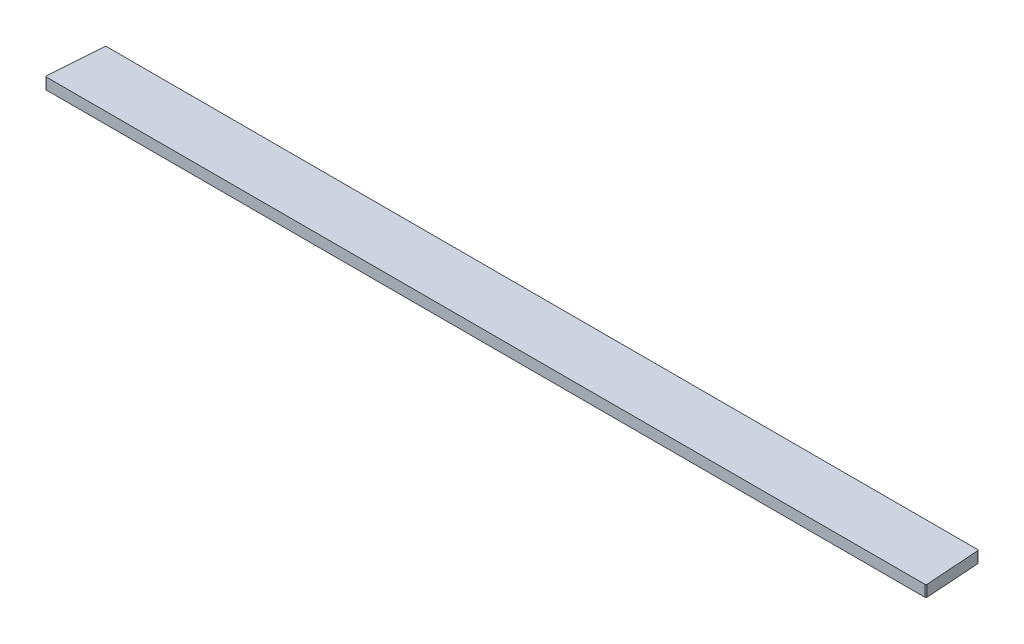
SolidWorks part; units mm, degrees
material "MS-Grade 400"
ref_plane "Front Plane" through (0, 0, 0) normal (0, 0, 1) x (1, 0, 0)
ref_plane "Top Plane" through (0, 0, 0) normal (0, 1, 0) x (1, 0, 0)
ref_plane "Right Plane" through (0, 0, 0) normal (1, 0, 0) x (0, 0, -1)
sketch "Sketch1" plane through (0, 0, 0) normal (0, 1, 0) x (1, 0, 0)
  line L0 (0, 0) -> (0, 50) construction
  line L1 (-386.5037, 50) -> (386.5037, 50)
  line L2 (-386.5037, 50) -> (-390, 0)
  line L3 (-390, 0) -> (390, 0)
  line L4 (386.5037, 50) -> (390, 0)
  dimension "D1" = 780
  dimension "D2" = 50
  dimension "D3" = 86
sheet metal parameters "Sheet-Metal1" thickness 10 parameters "D1"=92
base flange "Base-Flange1" sketch "Sketch1" thickness 10 reverse thickness direction no parameters "D1"=92
fillet "Fillet-1.0" radius 1 4 edges at (390, -5, 0) (386.5037, -5, -50) (-386.5037, -5, -50) (-390, -5, 0)
flat pattern "Flat-Pattern1" [suppressed]
sketch "Bend-Lines1" plane through (0, 0, 0) normal (0, 1, 0) x (1, 0, 0)
sketch3d "Bounding-Box1" [suppressed]
  line L0 (385, 0, 0) -> (-385, 0, 0) construction
  line L1 (385, 50, 0) -> (-385, 50, 0) construction
  line L2 (385, 0, 0) -> (385, 50, 0) construction
  line L3 (-385, 0, 0) -> (-385, 50, 0) construction
